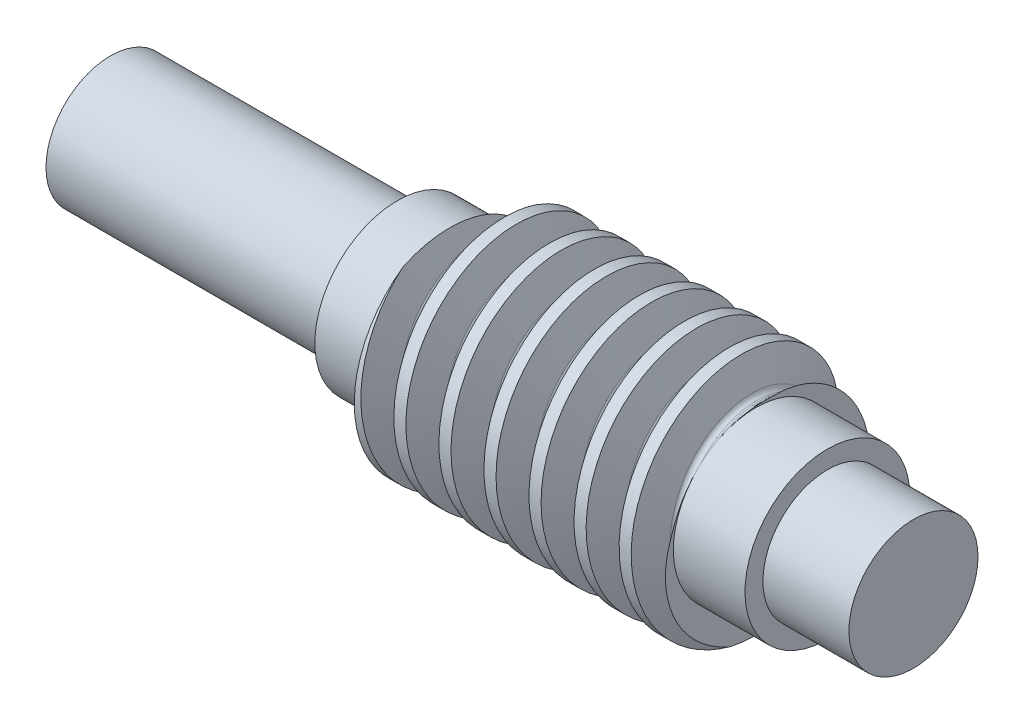
SolidWorks part; units mm, degrees
note: '?' marks a value the reader was unsure of.
ref_plane "前视基准面" through (0, 0, 0) normal (0, 0, 1) x (1, 0, 0)
ref_plane "上视基准面" through (0, 0, 0) normal (0, 1, 0) x (1, 0, 0)
ref_plane "右视基准面" through (0, 0, 0) normal (1, 0, 0) x (0, 0, -1)
ref_axis "基准轴1" through (-10.9638, 0, 0) along (1, 0, 0)?
sketch "草图1" plane through (0, 0, 0) normal (0, 0, 1) x (1, 0, 0)
  line L0 (-56.8494, 0) -> (118.6822, 0) construction
  line L1 (0, 48.1623) -> (0, -71.9241) construction
  line L2 (0, 8) -> (0, 0)
  line L3 (-10.9638, 0) -> (40.5935, 0) construction
  line L7 (0, 8) -> (20, 8)
  line L13 (0, 0) -> (20, 0)
  line L14 (20, 0) -> (20, 8)
  dimension "da1" = 8
  dimension "B1" = 20
revolve "旋转1" add sketch "草图1" angle 360 about L0
sketch "草图2" plane through (0, 0, 0) normal (1, 0, 0) x (0, 0, -1)
  circle A0 centre (0, 0) radius 9
  dimension "d1" = 18
sketch "草图3" plane through (0, 0, 0) normal (0, 0, 1) x (1, 0, 0)
  line L0 (0, 25.9401) -> (0, 0) construction
  line L1 (-3.4481, 8) -> (-1.1494, 8)
  line L2 (0, 8) -> (20, 8) construction
  line L3 (-1.1494, 8) -> (-1.8773, 6)
  line L4 (-2.2344, 5.75) -> (-2.3631, 5.75)
  line L5 (-2.2987, 8) -> (-2.2987, 5.75) construction
  line L6 (0, 0) -> (8.7963, 0) construction
  line L7 (-3.0841, 7) -> (-1.5133, 7) construction
  line L8 (-2.7202, 6) -> (-3.4481, 8)
  line L9 (-3.4481, 8) -> (-3.4481, -8) construction
  line L10 (-2.2987, 8) -> (0, 8) construction
  arc A0 (-2.7202, 6) -> (-2.3631, 5.75) centre (-2.3631, 6.13) ccw
  arc A1 (-2.2344, 5.75) -> (-1.8773, 6) centre (-2.2344, 6.13) ccw
  point P14 (-2.6292, 5.75)
  point P19 (-1.9683, 5.75)
  dimension "ppn" = 0.38
  dimension "d1" = 14
  dimension "0.5px" = 1.5708
  dimension "aa1" = 20
  dimension "aa" = 16
  dimension "df1" = 11.5
sketch "草图4" plane through (0, 0, 0) normal (1, 0, 0) x (0, 0, -1)
  circle A0 centre (0, 0) radius 5.75
sketch "草图5" plane through (20, 0, 0) normal (1, 0, 0) x (0, 0, -1)
  circle A0 centre (0, 0) radius 5.75 construction
  circle A1 centre (0, 0) radius 5.75
curve "螺旋线/涡状线1" pitch 3.1416 height 30.6 turns 9.7403
sweep "切除-扫描1" cut profiles "草图3" path "螺旋线/涡状线1"
extrude "凸台-拉伸1" add sketch "草图4" against normal blind 5
extrude "凸台-拉伸2" add sketch "草图5" along normal blind 5
sketch "草图6" plane through (-5, 0, 0) normal (-1, 0, 0) x (0, 0, 1)
  circle A0 centre (0, 0) radius 4.5
  dimension "D1" = 9
extrude "凸台-拉伸3" add sketch "草图6" along normal blind 20
sketch "草图7" plane through (25, 0, 0) normal (1, 0, 0) x (0, 0, -1)
  circle A1 centre (0, 0) radius 4.5
  circle A2 centre (0, 0) radius 4.5
  dimension "D1" = 0
extrude "凸台-拉伸4" add sketch "草图7" along normal blind 6
equation "\"aa1@草图3\" = \"aa1@草图3\""
